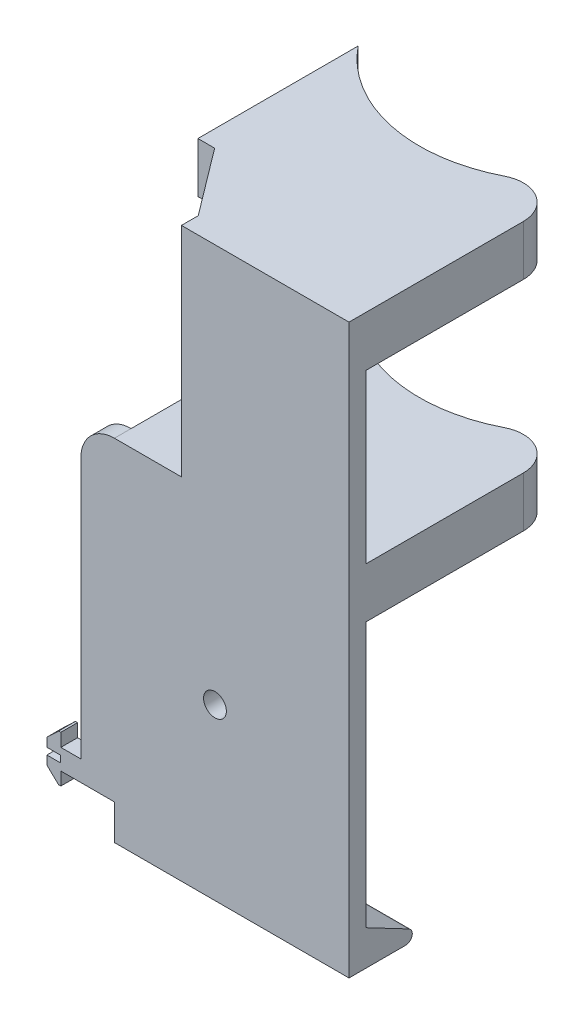
SolidWorks part; units mm, degrees
ref_plane "Front Plane" through (0, 0, 0) normal (0, 0, 1) x (1, 0, 0)
ref_plane "Top Plane" through (0, 0, 0) normal (0, 1, 0) x (1, 0, 0)
ref_plane "Right Plane" through (0, 0, 0) normal (1, 0, 0) x (0, 0, -1)
sketch "Sketch2" plane through (0, 0, 0) normal (0, 0, 1) x (1, 0, 0)
  line L1 (-5.1524, -3.6183) -> (-1.6411, -6.95)
  line L2 (-1.6411, -6.95) -> (-1, -6.95)
  line L6 (-5.1524, -3.6183) -> (-5.1524, 3.6183)
  line L7 (-1, -6.95) -> (-1, 6.95)
  line L8 (0, 0) -> (-6.1524, 0) construction
  line L9 (-1.6411, 6.95) -> (-1, 6.95)
  line L10 (-5.1524, 3.6183) -> (-1.6411, 6.95)
  line L11 (-1, -3.05) -> (5, -3.05)
  line L12 (-1, 3.05) -> (5, 3.05)
  line L13 (5, -3.05) -> (95, -3.05)
  line L14 (5, 3.05) -> (5, 155.95)
  line L15 (5, 155.95) -> (95, 155.95)
  line L16 (95, 155.95) -> (95, -3.05)
  line L17 (-1, 3.05) -> (-1, -3.05)
  point P11 (-1, 0)
  point P13 (-5.1524, 0)
  line B0 (0, -7.95) -> (-2.04, -7.95)
  line B1 (-6.1524, -4.048) -> (-6.1524, 4.048)
  line B2 (-2.04, 7.95) -> (0, 7.95)
  line B3 (0, 7.95) -> (0, -7.95)
  line B4 (-2.04, -7.95) -> (-6.1524, -4.048)
  line B5 (-6.1524, 4.048) -> (-2.04, 7.95)
  line B6 (0, -4.05) -> (0, 4.05) construction
  dimension "D1" = 1
  dimension "D2" = 1
  dimension "D3" = 1
  dimension "D4" = 1
  dimension "D5" = 1
  dimension "D6" = 6
  dimension "D7" = 90
  dimension "D8" = 159
sketch_block_instance "Extrusion Profile-2"
sketch_block "Block1" parameters "D1"=8.44, "D2"=2.6, "D3"=6, "D4"=16.7, "D6"=5.6686, "D7"=2.0404, "D8"=8.0963, "D9"=15.9, "D5"=2.4157
extrude "Boss-Extrude1" add sketch "Sketch2" against normal blind 5 contours L8 L17 L7 L9 L10 L6 | L7 L8 L6 L1 L2 | L12 B3 L11 L13 L16 L15 L14 | B3 L8 L7 L11 | L8 B3 L12 L17 region at (-2.846, -2.8739, 0) region at (-2.846, 2.8739, 0) region at (-0.5, -1.525, 0) region at (-0.5, 1.525, 0) region at (49.899, 76.2874, 0)
sketch "Sketch3" plane through (0, 155.95, 0) normal (0, 1, 0) x (1, 0, 0)
  line L0 (5, 5) -> (5, 0) construction
  line L1 (95, 5) -> (95, 0) construction
  line L2 (5, 101) -> (95, 101) construction
  line L3 (15, 72.7157) -> (15, 5)
  line L4 (5, 5) -> (95, 5) construction
  line L5 (15, 5) -> (85, 5)
  line L6 (50, 0) -> (50, -5.3878) construction
  line L7 (5, 0) -> (95, 0) construction
  line L8 (85, 72.7157) -> (85, 5)
  arc A0 (5, 101) -> (95, 101) centre (50, 101) ccw
  arc A1 (15, 72.7157) -> (85, 72.7157) centre (50, 101) ccw
  line M7 (95, 5) -> (5, 5)
  dimension "D1" = 45
  dimension "D2" = 96
  dimension "D3" = 35
extrude "Boss-Extrude2" add sketch "Sketch3" against normal blind 80 contours A0 L3 L8 M7 region at (50, 155.95, -33.2443)
sketch "Sketch4" plane through (0, 0, 0) normal (0, 0, 1) x (1, 0, 0)
  line L0 (-5.1524, 1) -> (-5.1524, -1)
  line L1 (-5.1524, -3.6183) -> (-5.1524, 3.6183) construction
  line L2 (-5.1524, -1) -> (-1.1524, -1)
  line L3 (-1.1524, -1) -> (-1.1524, 1)
  line L4 (-1.1524, 1) -> (-5.1524, 1)
  point P5 (-5.1524, 0)
  dimension "D1" = 2
  dimension "D2" = 4
extrude "Cut-Extrude1" cut sketch "Sketch4" against normal through all
sketch "Sketch5" plane through (15, 0, 0) normal (-1, 0, 0) x (0, 0, 1)
  line L0 (-5, 3.05) -> (-5, 155.95) construction
  line L1 (-5, 140.95) -> (-72.7157, 140.95)
  line L2 (-5, 140.95) -> (-5, 90.95)
  line L3 (-5, 90.95) -> (-72.7157, 90.95)
  line L4 (-72.7157, 140.95) -> (-72.7157, 90.95)
  line L5 (-72.7157, 75.95) -> (-72.7157, 155.95) construction
  line L6 (-72.7157, 155.95) -> (-5, 155.95) construction
  line L7 (-72.7157, 75.95) -> (-5, 75.95) construction
  dimension "D1" = 15
  dimension "D2" = 15
extrude "Cut-Extrude2" cut sketch "Sketch5" against normal through all
sketch "Sketch6" plane through (0, 155.95, 0) normal (0, 1, 0) x (1, 0, 0)
  line L0 (35, 0) -> (35, 5)
  line L1 (5, 0) -> (95, 0) construction
  line L2 (35, 5) -> (20, 24.9057)
  line L3 (20, 24.9057) -> (15, 24.9057)
  line L4 (15, 72.7157) -> (15, 5) construction
  line L5 (15, 24.9057) -> (15, 5)
  line L6 (15, 5) -> (5, 5)
  line L7 (5, 5) -> (5, 0)
  line L8 (5, 0) -> (35, 0)
  point P4 (35.7814, 0)
  dimension "D1" = 5
  dimension "D2" = 53
  dimension "D3" = 30
extrude "Cut-Extrude3" cut sketch "Sketch6" against normal blind 65
sketch "Sketch7" plane through (0, -3.05, 0) normal (0, -1, 0) x (1, 0, 0)
  line L1 (95, 0) -> (15, 0)
  line L2 (95, 0) -> (95, -5)
  line L3 (95, -5) -> (15, -5)
  line L4 (15, 0) -> (15, -5)
extrude "Boss-Extrude3" add sketch "Sketch7" along normal blind 10.5
sketch "Sketch8" plane through (15, 0, 0) normal (-1, 0, 0) x (0, 0, 1)
  line L0 (-5, -3.05) -> (-25, -13.55)
  line L1 (-25, -13.55) -> (-5, -13.55)
  line L2 (-5, -3.05) -> (-5, -13.55)
  dimension "D1" = 20
extrude "Boss-Extrude4" add sketch "Sketch8" against normal up to surface (80 mm away) up to face at (95, 71.2, -2.5)
fillet "Fillet1" radius 2 1 edges at (55, -13.55, -25)
fillet "Fillet2" radius 10 1 edges at (5, 90.95, -2.5)
sketch "Sketch9" plane through (0, 155.95, 0) normal (0, 1, 0) x (1, 0, 0)
  line L0 (85, 5) -> (85, 0)
  line L1 (35, 0) -> (95, 0) construction
  line L2 (85, 0) -> (95, 0)
  line L3 (95, 0) -> (95, 72.7157)
  line L4 (95, 72.7157) -> (85, 72.7157)
  line L5 (85, 72.7157) -> (85, 5) construction
  line L6 (85, 72.7157) -> (85, 5)
  arc A0 (15, 72.7157) -> (85, 72.7157) centre (50, 101) ccw construction
extrude "Cut-Extrude4" cut sketch "Sketch9" against normal through all
fillet "Fillet3" radius 10 1 edges at (85, 83.45, -72.7157)
sketch "Sketch10" plane through (0, 0, -5) normal (0, 0, -1) x (-1, 0, 0)
  circle A0 centre (-45, 37.0769) radius 3.4
  dimension "D1" = 6.8
extrude "Cut-Extrude5" cut sketch "Sketch10" against normal through all
